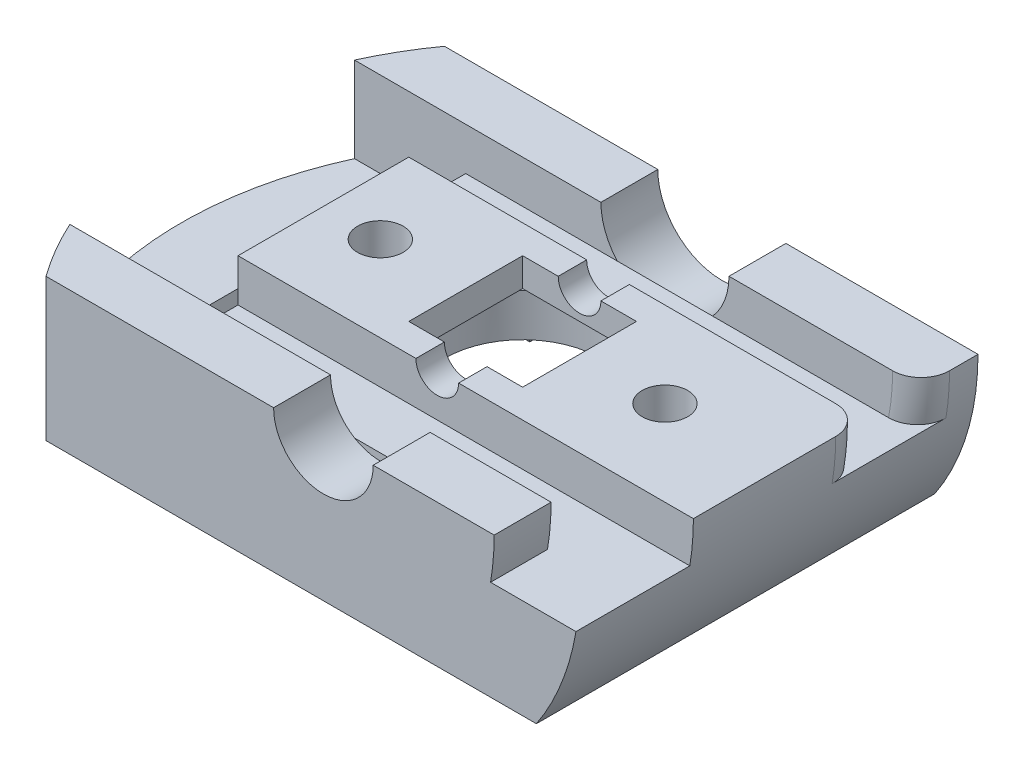
SolidWorks part; units mm, degrees
ref_plane "Front" through (0, 0, 0) normal (0, 0, 1) x (1, 0, 0)
ref_plane "Top" through (0, 0, 0) normal (0, 1, 0) x (1, 0, 0)
ref_plane "Right" through (0, 0, 0) normal (1, 0, 0) x (0, 0, -1)
sketch "Sketch1" plane through (0, 0, 0) normal (0, 1, 0) x (1, 0, 0)
  line L0 (21, 15) -> (21, 8)
  line L1 (12, 8) -> (12, 15) construction
  line L2 (12, 8) -> (12, 1) construction
  line L4 (12, 8) -> (21, 8) construction
  line L7 (21, 15) -> (12, 15)
  line L8 (12, 15) -> (2.2532, 15)
  line L10 (2.2532, 1) -> (12, 1)
  line L12 (12, 1) -> (21, 1)
  line L14 (21, 1) -> (21, 8)
  arc A1 (2.2532, 15) -> (2.2532, 1) centre (12, 8) ccw
extrude "Boss-Extrude1" add sketch "Sketch1" along normal blind 10
sketch "Sketch4" plane through (0, 0, 0) normal (0, 0, 1) x (1, 0, 0)
  line L0 (21, 5) -> (12, 5) construction
  line L2 (12, 14) -> (21, 14)
  line L3 (21, 14) -> (21, -4)
  line L4 (21, -4) -> (12, -4)
  arc A0 (12, 14) -> (12, -4) centre (12, 5) cw
extrude "Cut-Extrude3" cut sketch "Sketch4" against normal through all contours L2 A0 L3 | L3 A0 L4 region at (18.9897, -1.9897, 0) region at (18.9897, 11.9897, 0)
sketch "Sketch7" plane through (0, 0, 0) normal (0, 0, 1) x (1, 0, 0)
  line L0 (21, 5.5) -> (21, 11)
  line L1 (21, 5.5) -> (12, 5.5) construction
  line L2 (21, 11) -> (10, 11)
  line L4 (10, 11) -> (10, 7.5)
  line L5 (10, 7.5) -> (0, 7.5)
  line L7 (0, 7.5) -> (0, 3.5)
  line L8 (0, 3.5) -> (21, 3.5)
  line L9 (21, 3.5) -> (21, 5.5)
extrude "Cut-Extrude6" cut sketch "Sketch7" along normal blind 2 from offset 13 offset against normal yes
sketch "Sketch21" plane through (0, 0, 0) normal (0, 0, 1) x (1, 0, 0)
  line L0 (21, 5.5) -> (21, 11)
  line L1 (21, 5.5) -> (12, 5.5) construction
  line L2 (21, 11) -> (10, 11)
  line L4 (10, 11) -> (10, 7.5)
  line L5 (10, 7.5) -> (0, 7.5)
  line L7 (0, 7.5) -> (0, 3.5)
  line L8 (0, 3.5) -> (21, 3.5)
  line L9 (21, 3.5) -> (21, 5.5)
extrude "Cut-Extrude14" cut sketch "Sketch21" against normal blind 2 from offset 3 offset against normal yes
sketch "Sketch8" plane through (0, 0, 0) normal (0, 1, 0) x (1, 0, 0)
  circle A1 centre (12, 8) radius 2.75
extrude "Cut-Extrude7" cut sketch "Sketch8" against normal blind 2 from offset 10
sketch "Sketch10" plane through (0, 0, 0) normal (0, 0, 1) x (1, 0, 0)
  circle A0 centre (12, 5) radius 2.25
extrude "Cut-Extrude8" cut sketch "Sketch10" along normal blind 3 from offset 16 offset against normal yes
sketch "Sketch11" plane through (0, 0, 0) normal (1, 0, 0) x (0, 0, -1)
  line L0 (8, 0) -> (8, 2) construction
  line L2 (8, 2) -> (13, 2)
  line L3 (13, 2) -> (13, 8)
  line L4 (13, 8) -> (3, 8)
  line L5 (3, 8) -> (3, 2)
  line L6 (3, 2) -> (8, 2)
extrude "Cut-Extrude9" cut sketch "Sketch11" along normal blind 5
sketch "Sketch18" plane through (0, 0, 0) normal (0, 0, 1) x (1, 0, 0)
  circle A0 centre (12, 5) radius 0.75
extrude "Cut-Extrude12" cut sketch "Sketch18" against normal through all
sketch "Sketch19" plane through (0, 0, 0) normal (0, 1, 0) x (1, 0, 0)
  line L0 (10, 10) -> (14, 10)
  line L3 (14, 10) -> (14, 6)
  line L4 (14, 6) -> (10, 6)
  line L5 (10, 6) -> (10, 10)
extrude "Cut-Extrude13" cut sketch "Sketch19" along normal mid plane 2 from offset 5
sketch "Sketch5" plane through (0, 0, 0) normal (0, 0, 1) x (1, 0, 0)
  circle A1 centre (12, 5) radius 1.75
extrude "Cut-Extrude15" cut sketch "Sketch5" against normal blind 2 from offset 1 offset against normal yes
sketch "Sketch26" plane through (0, 0, 0) normal (0, 0, 1) x (1, 0, 0)
  line L0 (16.4833, 10) -> (19.4833, 10)
  line L3 (20.8741, 3.5) -> (17.8741, 3.5)
  arc A1 (20.8741, 3.5) -> (19.4833, 10) centre (12, 5) ccw
  arc A2 (17.8741, 3.5) -> (16.4833, 10) centre (9, 5) ccw
extrude "Cut-Extrude16" cut sketch "Sketch26" against normal blind 2 from offset 1 offset against normal yes
fillet "Fillet2" radius 0.5 1 edges at (12, 8, -5.25)
fillet "Fillet3" radius 1 4 edges at (20.8008, 6.8831, -13) (14.7417, 10, -13) (20.8008, 6.8831, -11) (14.7417, 10, -11)
sketch "Sketch3" plane through (28.2876, 0, 0) normal (0, 1, 0) x (1, 0, 0)
  line L0 (-25.2876, 12.5) -> (-20.5376, 12.5)
  line L1 (-25.2876, 3.5) -> (-20.5376, 3.5)
  line L26 (-16.2876, 8) -> (-9.2876, 8) construction
  line L27 (-16.2876, 8) -> (-25.2876, 8) construction
  line L28 (-16.2876, 8) -> (-16.2876, 2.5) construction
  line L29 (-16.2876, 8) -> (-16.2876, 13.5) construction
  line L30 (-9.2876, 8) -> (-9.2876, 9.5001)
  line L31 (-9.2876, 9.5001) -> (-10.7911, 9.5001)
  line L32 (-10.7911, 9.5001) -> (-12.2911, 9.5001) construction
  line L33 (-12.2911, 9.5001) -> (-12.2911, 12.5001) construction
  line L34 (-10.7911, 9.5001) -> (-12.2911, 12.5001)
  line L35 (-12.2911, 12.5001) -> (-12.2911, 13.5)
  line L36 (-12.2911, 13.5) -> (-16.2876, 13.5)
  line L37 (-16.2876, 13.5) -> (-20.5376, 13.5)
  line L38 (-20.5376, 13.5) -> (-20.5376, 12.5)
  line L40 (-25.2876, 12.5) -> (-25.2876, 8)
  line L41 (-9.2876, 8) -> (-9.2876, 6.5)
  line L42 (-9.2876, 6.5) -> (-10.7876, 6.5)
  line L43 (-10.7876, 6.5) -> (-12.2876, 6.5) construction
  line L44 (-12.2876, 6.5) -> (-12.2876, 3.5) construction
  line L45 (-10.7876, 6.5) -> (-12.2876, 3.5)
  line L46 (-12.2876, 3.5) -> (-12.2876, 2.5)
  line L47 (-12.2876, 2.5) -> (-16.2876, 2.5)
  line L48 (-16.2876, 2.5) -> (-20.5376, 2.5)
  line L49 (-20.5376, 2.5) -> (-20.5376, 3.5)
  line L51 (-25.2876, 3.5) -> (-25.2876, 8)
extrude "Pot Insert" cut sketch "Sketch3" along normal blind 2.5
sketch "Sketch6" plane through (0, 0, 0) normal (0, 1, 0) x (1, 0, 0)
  circle A1 centre (12, 8) radius 2.75
extrude "Pot Hole" cut sketch "Sketch6" along normal blind 1.5 from offset 2.5
sketch "Sketch14" plane through (0, 0, 0) normal (0, 1, 0) x (1, 0, 0)
  line L0 (12, 8) -> (17, 8) construction
  line L1 (12, 8) -> (7, 8) construction
  circle A0 centre (7, 8) radius 0.8
  circle A1 centre (17, 8) radius 0.8
extrude "Screw Holes" cut sketch "Sketch14" against normal blind 9 from offset 11
sketch "Sketch15" plane through (0, 0, 0) normal (0, 1, 0) x (1, 0, 0)
  circle A0 centre (7, 8) radius 1.25
  circle A1 centre (17, 8) radius 1.25
extrude "Screw Heads" cut sketch "Sketch15" against normal blind 2 from offset 10
sketch "Sketch13" plane through (0, 0, 0) normal (0, 1, 0) x (1, 0, 0)
  line L1 (21, 15) -> (0, 15)
  line L2 (21, 15) -> (21, 0)
  line L3 (21, 0) -> (0, 0)
  line L4 (0, 15) -> (0, 0)
extrude "Cut-Extrude11" cut sketch "Sketch13" against normal blind 5 from offset 10
